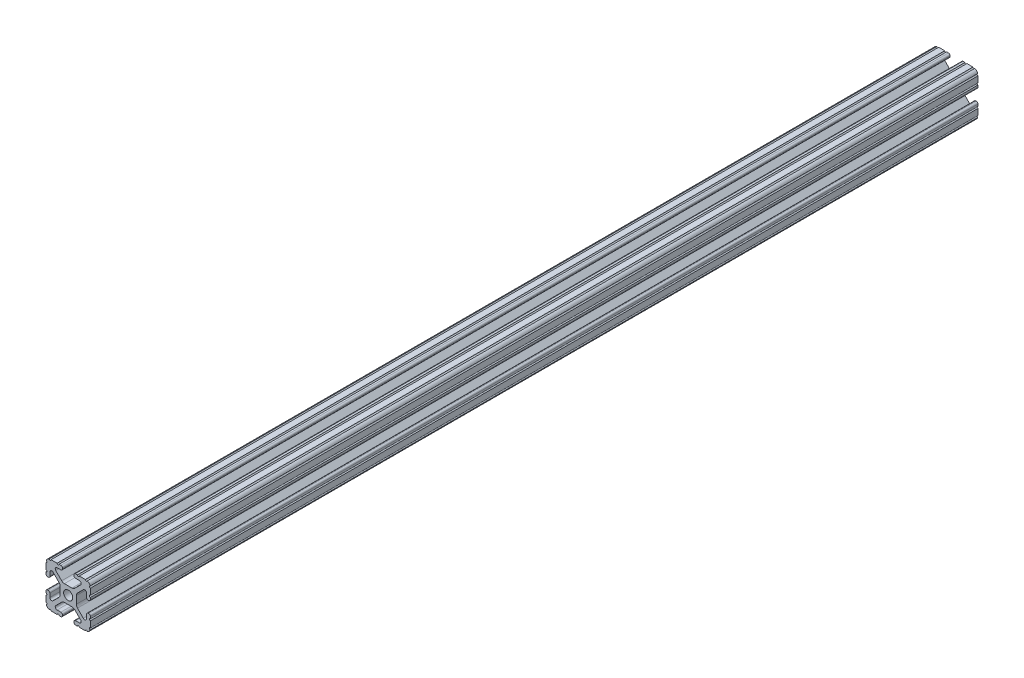
SolidWorks part; units mm, degrees
ref_plane "Front Plane" through (0, 0, 0) normal (0, 0, 1) x (1, 0, 0)
ref_plane "Top Plane" through (0, 0, 0) normal (0, 1, 0) x (1, 0, 0)
ref_plane "Right Plane" through (0, 0, 0) normal (1, 0, 0) x (0, 0, -1)
sketch "Sketch2" plane through (0, 0, 0) normal (0, 0, 1) x (1, 0, 0)
  line L0 (0, 12.7) -> (0, -12.7) construction
  line L1 (-12.7, 0) -> (12.7, 0) construction
  line L2 (3.2512, -12.7) -> (12.7, -12.7)
  line L3 (12.7, -12.7) -> (12.7, -3.2512)
  line L4 (3.2512, -12.7) -> (3.2512, -10.4902)
  line L5 (3.2512, -10.4902) -> (8.9276, -10.4902)
  line L6 (8.9276, -10.4902) -> (3.0856, -4.6482)
  line L7 (0, 0) -> (12.7, -12.7) construction
  line L8 (12.7, -3.2512) -> (10.4902, -3.2512)
  line L9 (10.4902, -3.2512) -> (10.4902, -8.9276)
  line L10 (10.4902, -8.9276) -> (4.6482, -3.0856)
  circle A0 centre (0, 0) radius 2.6035
  arc A1 (6.3485, -10.4902) -> (7.1039, -8.6665) centre (6.3485, -9.4219) ccw construction
  point P8 (0, -4.6482)
  dimension "Center Hole Diameter" = 5.207
  dimension "Rail Height" = 25.4
  dimension "Rail Width" = 25.4
  dimension "T-Slot Width" = 6.5024
  dimension "Slot Inner Width" = 14.8336
  dimension "Thickness" = 2.2098
  dimension "Slot Depth" = 5.842
  dimension "D1" = 2.2098
sketch "Sketch3" plane through (0, 0, 0) normal (1, 0, 0) x (0, 0, -1)
  line L0 (-1524, -12.7) -> (1524, -12.7) construction
  line L1 (-1498.6, 0) -> (1498.6, 0) construction
  dimension "Length" = 3048
  dimension "D1" = 25.4
sketch "Sketch4" plane through (0, 0, 0) normal (0, 0, 1) x (1, 0, 0)
  line L0 (4.1904, -12.7) -> (10.1173, -12.7)
  line L1 (3.2512, -12.7) -> (12.7, -12.7) construction
  line L2 (3.2512, -12.7) -> (3.2512, -10.4902) construction
  line L3 (3.2512, -10.4902) -> (8.9276, -10.4902) construction
  line L4 (3.2512, -11.4294) -> (3.2512, -11.7608)
  line L5 (4.1904, -10.4902) -> (6.3485, -10.4902)
  line L6 (0, -4.6482) -> (2.164, -4.6482)
  line L7 (8.9276, -10.4902) -> (3.0856, -4.6482) construction
  line L8 (3.7373, -5.2999) -> (7.1039, -8.6665)
  line L9 (12.7, -12.7) -> (12.7, -3.2512) construction
  line L10 (10.4902, -8.9276) -> (4.6482, -3.0856) construction
  line L11 (10.4902, -3.2512) -> (10.4902, -8.9276) construction
  line L12 (10.4902, -6.3485) -> (10.4902, -4.1904)
  line L13 (12.7, -3.2512) -> (10.4902, -3.2512) construction
  line L14 (11.4294, -3.2512) -> (11.7608, -3.2512)
  line L15 (12.7, -4.1904) -> (12.7, -10.1173)
  line L16 (8.6665, -7.1039) -> (5.2999, -3.7373)
  line L17 (4.6482, 0) -> (4.6482, -2.164)
  line L18 (-12.7, 0) -> (12.7, 0) construction
  line L19 (0, -4.6482) -> (0, -2.6035)
  line L20 (0, 12.7) -> (0, -12.7) construction
  line L21 (4.6482, 0) -> (2.6035, 0)
  arc A0 (3.2512, -11.7608) -> (4.1904, -12.7) centre (4.1904, -11.7608) ccw
  arc A2 (3.2512, -11.4294) -> (4.1904, -10.4902) centre (4.1904, -11.4294) cw
  arc A3 (6.3485, -10.4902) -> (7.1039, -8.6665) centre (6.3485, -9.4219) ccw
  arc A4 (2.164, -4.6482) -> (3.7373, -5.2999) centre (2.164, -6.8732) cw
  arc A5 (10.1173, -12.7) -> (12.7, -10.1173) centre (10.1173, -10.1173) ccw
  arc A6 (8.6665, -7.1039) -> (10.4902, -6.3485) centre (9.4219, -6.3485) ccw
  arc A7 (10.4902, -4.1904) -> (11.4294, -3.2512) centre (11.4294, -4.1904) cw
  arc A8 (11.7608, -3.2512) -> (12.7, -4.1904) centre (11.7608, -4.1904) cw
  arc A9 (5.2999, -3.7373) -> (4.6482, -2.164) centre (6.8732, -2.164) cw
  circle A10 centre (0, 0) radius 2.6035 construction
  arc A11 (0, -2.6035) -> (2.6035, 0) centre (0, 0) ccw
  dimension "D1" = 2.5827
  dimension "D2" = 2.225
  dimension "D3" = 0.9392
extrude "Boss-Extrude1" add sketch "Sketch4" along normal mid plane 3048
sketch "Sketch5" plane through (0, 0, 0) normal (0, 0, 1) x (1, 0, 0)
  line L0 (3.2512, -12.7) -> (12.7, -12.7) construction
  line L1 (4.1904, -10.4902) -> (6.3485, -10.4902) construction
  line L3 (0, 0) -> (12.7, -12.7) construction
  line L4 (6.3485, -10.4902) -> (6.3485, -12.7) construction
  line L5 (8.9276, -10.4902) -> (3.0856, -4.6482) construction
  circle A0 centre (10.3562, -12.7) radius 0.5524
  circle A1 centre (5.796, -12.7) radius 0.5524
  circle A2 centre (12.7, -10.3562) radius 0.5524
  circle A3 centre (12.7, -5.796) radius 0.5524
  point P10 (5.2694, -10.4902)
  point P12 (9.4219, -6.3485)
  dimension "D1" = 1.1049
extrude "Cut-Extrude1" cut sketch "Sketch5" against normal through all both and the other way through all
mirror "Mirror1" about plane through (0, 0, 0) normal (1, 0, 0) of bodies 137 134
mirror "Mirror2" about plane through (0, 0, 0) normal (0, 1, 0) of bodies 135
sketch "Sketch8" plane through (0, 0, 0) normal (0, 1, 0) x (1, 0, 0)
  line L0 (-12.58, 1524) -> (-12.58, -1524) construction
  line L1 (-25.28, 1536.7) -> (25.28, 1536.7)
  line L2 (-25.28, 1536.7) -> (-25.28, -1016)
  line L3 (-25.28, -1016) -> (25.28, -1016)
  line L4 (25.28, 1536.7) -> (25.28, -1016)
  line L5 (12.58, 1524) -> (12.58, -1524) construction
  line L7 (-6.3485, -1524) -> (-9.8037, -1524) construction
  dimension "D1" = 12.7
  dimension "D2" = 12.7
  dimension "D3" = 12.7
  dimension "D4" = 508
extrude "Cut-Extrude2" cut sketch "Sketch8" against normal through all both and the other way through all
equation "\"D1@Boss-Extrude1\"=\"Length@Sketch3\""
equation "\"D1@Sketch2\"=\"Thickness@Sketch2\""
equation "\"D2@Sketch4\"=\"Slot Inner Width@Sketch2\"*0.15"
equation "\"D1@Sketch4\"=\"D3@Sketch4\"*2.75"
equation "\"D3@Sketch4\"=\"Thickness@Sketch2\"*0.425"
equation "\"D1@Sketch5\"=\"Thickness@Sketch2\"*0.5"
